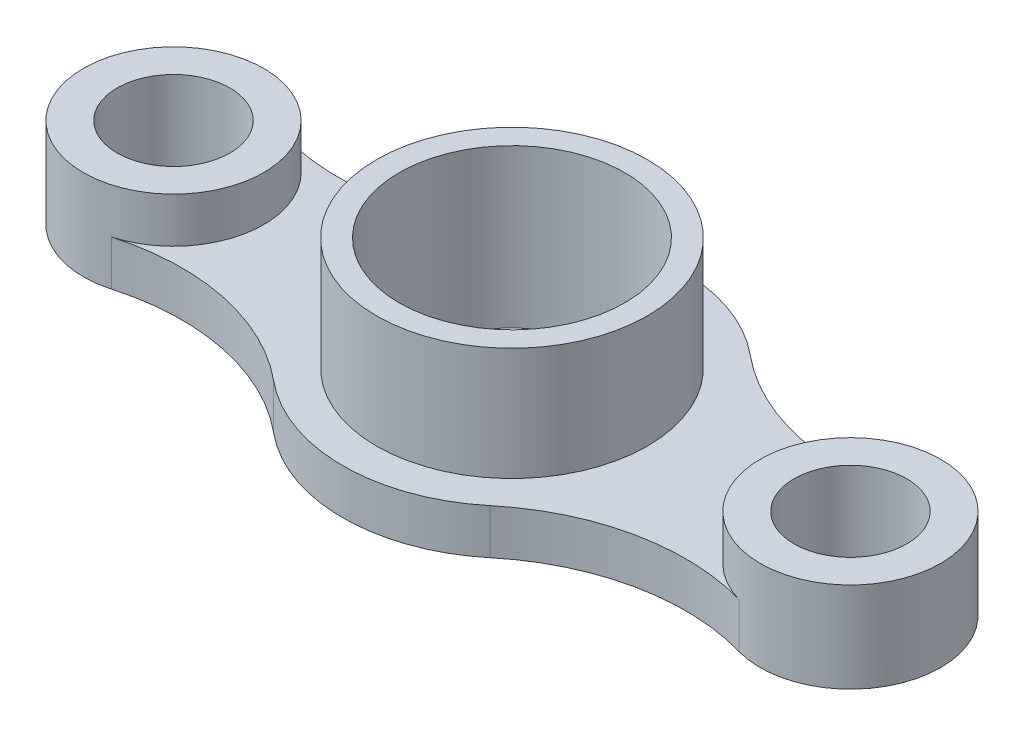
SolidWorks part; units mm, degrees
ref_plane "Front Plane" through (0, 0, 0) normal (0, 0, 1) x (1, 0, 0)
ref_plane "Top Plane" through (0, 0, 0) normal (0, 1, 0) x (1, 0, 0)
ref_plane "Right Plane" through (0, 0, 0) normal (1, 0, 0) x (0, 0, -1)
sketch "Sketch1" plane through (0, 0, 0) normal (0, 1, 0) x (1, 0, 0)
  line L0 (0, -5955.0605) -> (0, 291797.9643) construction
  circle A0 centre (0, 0) radius 50
  circle A1 centre (0, 0) radius 60
  arc A2 (-47.8929, -57.7172) -> (47.8929, -57.7172) centre (0, 0) ccw
  circle A3 centre (-150, 0) radius 25
  circle A4 centre (-150, 0) radius 40
  arc A5 (-139.0714, 38.4781) -> (-47.8929, 57.7172) centre (-111.75, 134.6734) ccw
  arc A6 (-139.0714, -38.4781) -> (-47.8929, -57.7172) centre (-111.75, -134.6734) cw
  arc A7 (139.0714, -38.4781) -> (47.8929, -57.7172) centre (111.75, -134.6734) ccw
  arc A8 (139.0714, 38.4781) -> (47.8929, 57.7172) centre (111.75, 134.6734) cw
  circle A9 centre (150, 0) radius 40
  circle A10 centre (150, 0) radius 25
  arc A11 (47.8929, 57.7172) -> (-47.8929, 57.7172) centre (0, 0) ccw
  point P16 (-196.405, -39.8858)
  dimension "D1" = 100
  dimension "D2" = 120
  dimension "D3" = 150
  dimension "D4" = 50
  dimension "D5" = 80
  dimension "D6" = 100
  dimension "D7" = 150
extrude "Boss-Extrude1" add sketch "Sketch1" along normal blind 20 contours A2 L0 A1 A11 A5 A4 A6 | L0 A2 A7 A9 A8 A11 A1 region at (-68.7035, 0, 0) region at (68.7035, 0, 0)
extrude "Boss-Extrude2" add sketch "Sketch1<3>" along normal blind 40 contours A4 A3 | A9 A10 region at (-188.8686, 0, 0) region at (111.1314, 0, 0)
sketch "Sketch1<3>" plane through (0, 0, 0) normal (0, 1, 0) x (1, 0, 0) same geometry as "Sketch1"
extrude "Boss-Extrude3" add sketch "Sketch1<4>" along normal blind 70 contours L0 A1 A0 | A1 L0 A0 region at (-58.6584, 0, 0) region at (1.3416, 0, 55)
sketch "Sketch1<4>" plane through (0, 0, 0) normal (0, 1, 0) x (1, 0, 0) same geometry as "Sketch1"
